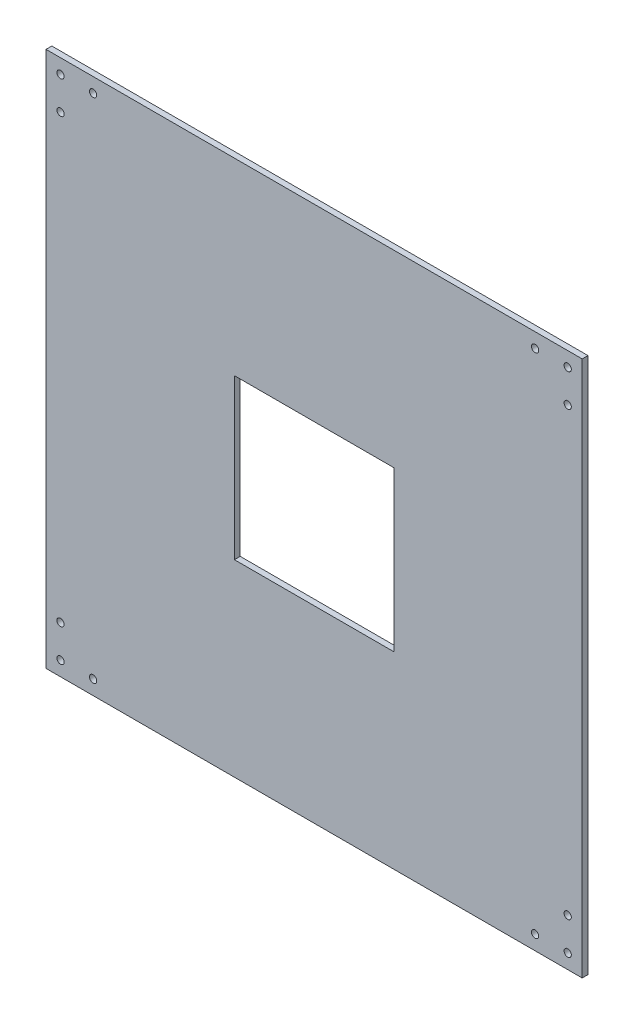
SolidWorks part; units mm, degrees
ref_plane "前视基准面" through (0, 0, 0) normal (0, 0, 1) x (1, 0, 0)
ref_plane "上视基准面" through (0, 0, 0) normal (0, 1, 0) x (1, 0, 0)
ref_plane "右视基准面" through (0, 0, 0) normal (1, 0, 0) x (0, 0, -1)
sketch "草图1" plane through (0, 0, 0) normal (0, 0, 1) x (1, 0, 0)
  line L1 (185, -185) -> (-185, -185)
  line L2 (185, -185) -> (185, 185)
  line L3 (185, 185) -> (-185, 185)
  line L4 (-185, -185) -> (-185, 185)
  line L5 (185, -185) -> (-185, 185) construction
  line L6 (185, 185) -> (-185, -185) construction
  point P0 (0, 0)
  dimension "D1" = 370
  dimension "D2" = 370
extrude "凸台-拉伸1" add sketch "草图1" along normal blind 4
sketch "草图2" plane through (0, 0, 4) normal (0, 0, 1) x (1, 0, 0)
  line L0 (-165, -175) -> (-152.5, -175) construction
  line L1 (-185, -185) -> (-165, -185) construction
  line L2 (-185, -185) -> (-185, -165) construction
  line L3 (-185, -165) -> (-165, -165) construction
  line L4 (-165, -185) -> (-165, -165) construction
  line L5 (-175, -165) -> (-175, -152.5) construction
  circle A0 centre (-175, -175) radius 2.5
  circle A1 centre (-152.5, -175) radius 2.5
  circle A2 centre (-175, -152.5) radius 2.5
  circle A3 centre (-152.5, 175) radius 2.5
  circle A4 centre (-175, 152.5) radius 2.5
  circle A5 centre (-175, 175) radius 2.5
  circle A6 centre (175, 152.5) radius 2.5
  circle A7 centre (152.5, 175) radius 2.5
  circle A8 centre (175, 175) radius 2.5
  circle A9 centre (152.5, -175) radius 2.5
  circle A10 centre (175, -152.5) radius 2.5
  circle A11 centre (175, -175) radius 2.5
  point P34 (0, 0)
  dimension "D3" = 10
  dimension "D4" = 10
  dimension "D5" = 5
  dimension "D6" = 12.5
  dimension "D7" = 5
  dimension "D9" = 5
  dimension "D1" = 20
  dimension "D2" = 20
  dimension "D8" = 12.5
  dimension "D10" = 4
extrude "切除-拉伸1" cut sketch "草图2" against normal through all
sketch "草图3" plane through (0, 0, 0) normal (0, 0, -1) x (-1, 0, 0)
  line L1 (55, -55) -> (-55, -55)
  line L2 (55, -55) -> (55, 55)
  line L3 (55, 55) -> (-55, 55)
  line L4 (-55, -55) -> (-55, 55)
  line L5 (55, -55) -> (-55, 55) construction
  line L6 (55, 55) -> (-55, -55) construction
  point P0 (0, 0)
  dimension "D1" = 110
  dimension "D2" = 110
extrude "切除-拉伸2" cut sketch "草图3" against normal blind 10
